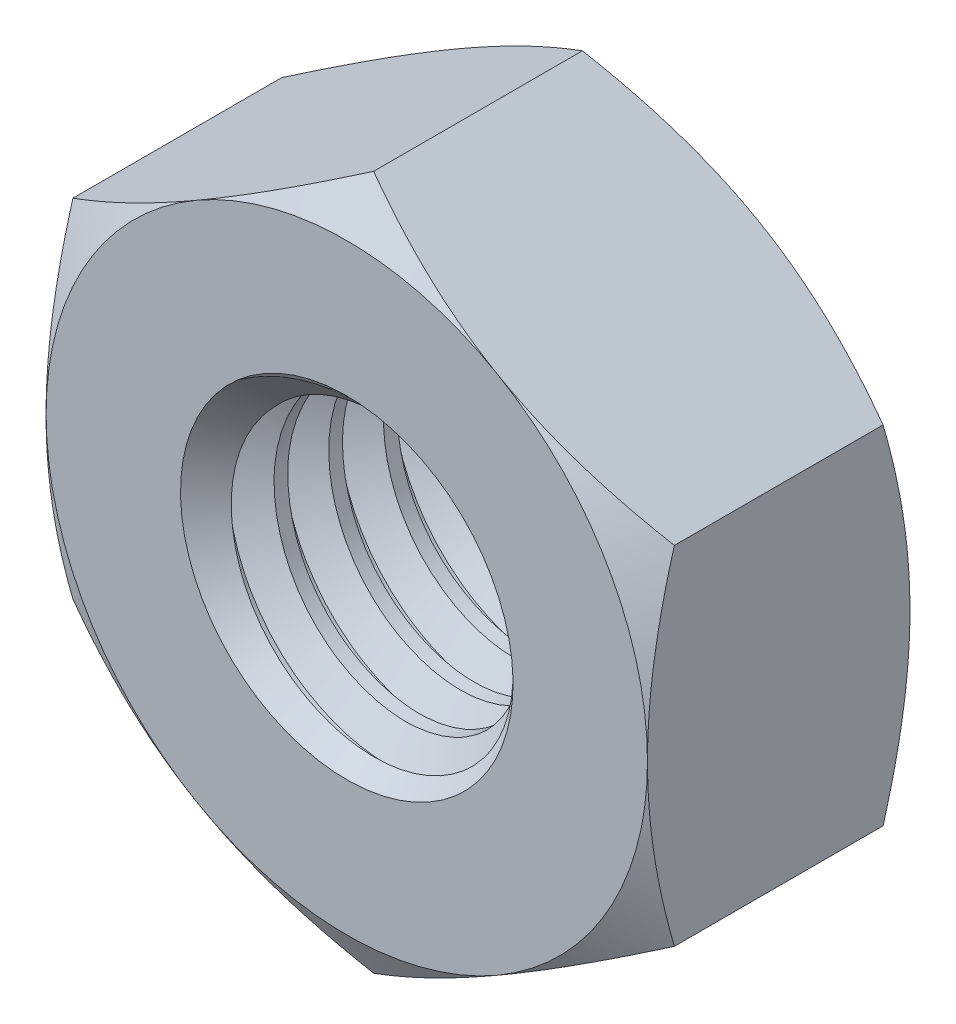
SolidWorks part; units mm, degrees
material "Plain Carbon Steel"
ref_plane "Front Plane" through (0, 0, 0) normal (0, 0, 1) x (1, 0, 0)
ref_plane "Top Plane" through (0, 0, 0) normal (0, 1, 0) x (1, 0, 0)
ref_plane "Right Plane" through (0, 0, 0) normal (1, 0, 0) x (0, 0, -1)
sketch "Sketch2" plane through (0, 0, 0) normal (0, 0, 1) x (1, 0, 0)
  line L0 (2.75, 1.5877) -> (2.75, -1.5877)
  line L1 (-2.75, 1.5877) -> (-2.75, -1.5877)
  line L2 (2.75, 1.5877) -> (0, 3.1754)
  line L3 (0, 3.1754) -> (-2.75, 1.5877)
  line L4 (-2.75, -1.5877) -> (0, -3.1754)
  line L5 (0, -3.1754) -> (2.75, -1.5877)
  circle A0 centre (0, 0) radius 1.25
  dimension "D3" = 2.5
  dimension "D1" = 5.5
  dimension "D2" = 120
  dimension "D4" = 2.75
extrude "Boss-Extrude1" add sketch "Sketch2" along normal mid plane 2.4
sketch "Sketch3" plane through (0, 0, -1.2) normal (0, 0, -1) x (-1, 0, 0)
  line L0 (0, 3.1754) -> (2.75, 1.5877) construction
  line L1 (-2.75, 1.5877) -> (0, 3.1754) construction
  line L2 (-2.75, 1.5877) -> (-2.75, -1.5877) construction
  line L3 (0, -3.1754) -> (-2.75, -1.5877) construction
  line L4 (2.75, -1.5877) -> (0, -3.1754) construction
  line L5 (2.75, 1.5877) -> (2.75, -1.5877) construction
  line L6 (0, 3.1754) -> (2.75, 1.5877) construction
  line L7 (-2.75, 1.5877) -> (0, 3.1754) construction
  line L8 (-2.75, 1.5877) -> (-2.75, -1.5877) construction
  line L9 (0, -3.1754) -> (-2.75, -1.5877) construction
  line L10 (2.75, -1.5877) -> (0, -3.1754) construction
  line L11 (2.75, 1.5877) -> (2.75, -1.5877) construction
  circle A0 centre (0, 0) radius 2.75 construction
sketch "Sketch4" plane through (0, 0, 0) normal (1, 0, 0) x (0, 0, -1)
  line L0 (1.2, -2.75) -> (1.2, 2.75) construction
  line L1 (1.2, -2.75) -> (1.2, 2.75) construction
  line L2 (1.2, 2.75) -> (1.2, 4.3287)
  line L3 (1.2, 4.3287) -> (0.2886, 4.3287)
  line L4 (0.2886, 4.3287) -> (1.2, 2.75)
  line L6 (-2.9945, 0) -> (4.4636, 0) construction
  dimension "D1" = 30
revolve "Cut-Revolve2" cut sketch "Sketch4" angle 360 about L6
mirror "Mirror1" about plane through (0, 0, 0) normal (0, 0, 1) of "Cut-Revolve2"
chamfer "Chamfer1" distance 0.2705 angle 45 2 edges at (1.25, 0, -1.2) (1.25, 0, 1.2)
ref_plane "Plane1" through (0, 0, -1.7) normal (0, 0, -1) x (-1, 0, 0)
sketch "Sketch5" plane through (0, 0, -1.7) normal (0, 0, -1) x (-1, 0, 0)
  circle A0 centre (0, 0) radius 1.25 construction
  circle A1 centre (0, 0) radius 1.25
curve "Helix/Spiral1" pitch 0.5 height 5 radius 1.25 centre (0, 0, -1.7) axis (0, 0, 1) start towards (-1, 0, 0)
sketch "Sketch6" plane through (0, 0, 0) normal (0, 1, 0) x (1, 0, 0)
  line L0 (1.25, 1.7) -> (-1.25, 1.7) construction
  line L1 (1.25, 1.7) -> (-1.25, 1.7) construction
  line L2 (-1.25, 3.2536) -> (-1.25, -1.7335) construction
  line L3 (-1.5205, 1.6687) -> (-1.5205, 1.7312)
  line L4 (-1.5205, 1.7312) -> (-0.9623, 2.0535)
  line L5 (-1.5205, 1.6687) -> (-0.9623, 1.3465)
  line L6 (-0.9623, 2.0535) -> (-0.9623, 1.3465)
  point P9 (-1.5205, 1.7)
  point P11 (-0.9623, 1.7)
  dimension "D1" = 60
  dimension "D2" = 0.0625
  dimension "D3" = 0.2705
sweep "Cut-Sweep1" cut profiles "Sketch6" path "Helix/Spiral1" align with end faces yes
